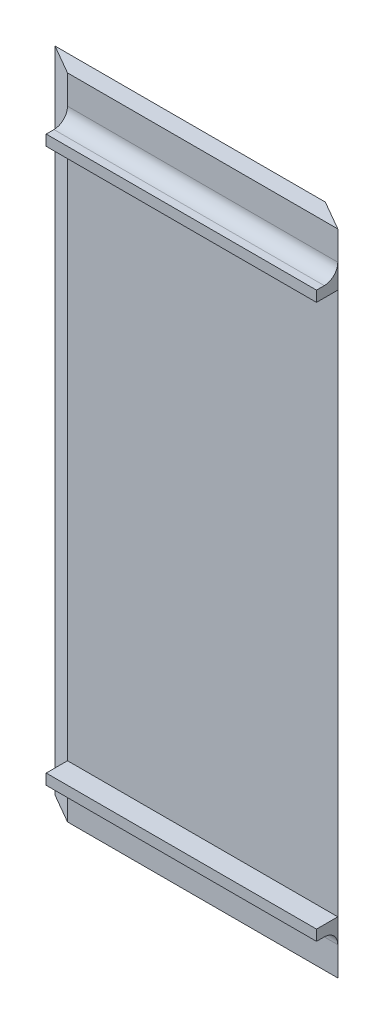
SolidWorks part; units mm, degrees
ref_plane "Front Plane" through (0, 0, 0) normal (0, 0, 1) x (1, 0, 0)
ref_plane "Top Plane" through (0, 0, 0) normal (0, 1, 0) x (1, 0, 0)
ref_plane "Right Plane" through (0, 0, 0) normal (1, 0, 0) x (0, 0, -1)
sketch "Sketch1" plane through (0, 0, 0) normal (0, 0, 1) x (1, 0, 0)
  line L0 (53.7926, 0) -> (53.7926, -121.92)
  line L1 (53.7926, -121.92) -> (2.9926, -121.92)
  line L2 (2.9926, -121.92) -> (2.9926, 0)
  line L3 (2.9926, 0) -> (53.7926, 0)
extrude "Boss-Extrude1" add sketch "Sketch1" against normal blind 3.2
sketch "Sketch2" plane through (0, -121.92, 0) normal (0, -1, 0) x (1, 0, 0)
  line L0 (53.7926, 0) -> (53.7926, -3.2)
  line L1 (53.7926, -3.2) -> (48.2501, -3.2)
  line L2 (2.9926, -3.2) -> (53.7926, -3.2) construction
  line L3 (-56.1926, -63.5) -> (53.7926, 0) construction
  line L4 (48.2501, -3.2) -> (53.7926, 0)
extrude "Cut-Extrude1" cut sketch "Sketch2" against normal through all
sketch "Sketch4" plane through (0, -121.92, 0) normal (0, -1, 0) x (1, 0, 0)
  line L0 (2.9926, 0) -> (2.9926, -3.2)
  line L1 (2.9926, -3.2) -> (-2.5499, -3.2)
  line L3 (-2.5499, -3.2) -> (2.9926, 0)
extrude "Boss-Extrude2" add sketch "Sketch4" against normal up to surface (121.92 mm away) up to face at (27.007, 0, -1.6)
sketch "Sketch5" plane through (0, 0, 0) normal (0, 0, 1) x (1, 0, 0)
  line L0 (53.7926, -9.96) -> (53.7926, -7.96)
  line L1 (53.7926, -121.92) -> (53.7926, 0) construction
  line L2 (53.7926, -7.96) -> (2.9926, -7.96)
  line L3 (2.9926, 0) -> (2.9926, -121.92) construction
  line L4 (2.9926, -7.96) -> (2.9926, -9.96)
  line L5 (2.9926, -9.96) -> (53.7926, -9.96)
  line L6 (0.4702, -10.46) -> (66.0702, -10.46) construction
  line L7 (53.7926, -60.96) -> (2.9926, -60.96) construction
  line L8 (2.9926, -111.96) -> (53.7926, -111.96)
  line L9 (2.9926, -113.96) -> (2.9926, -111.96)
  line L10 (53.7926, -113.96) -> (2.9926, -113.96)
  line L11 (53.7926, -111.96) -> (53.7926, -113.96)
  dimension "D1" = 2
  dimension "D2" = 0.5
extrude "Boss-Extrude3" add sketch "Sketch5" along normal blind 4
fillet "Fillet1" radius 2.54 2 edges at (28.3926, -7.96, 0) (28.3926, -113.96, 0)
